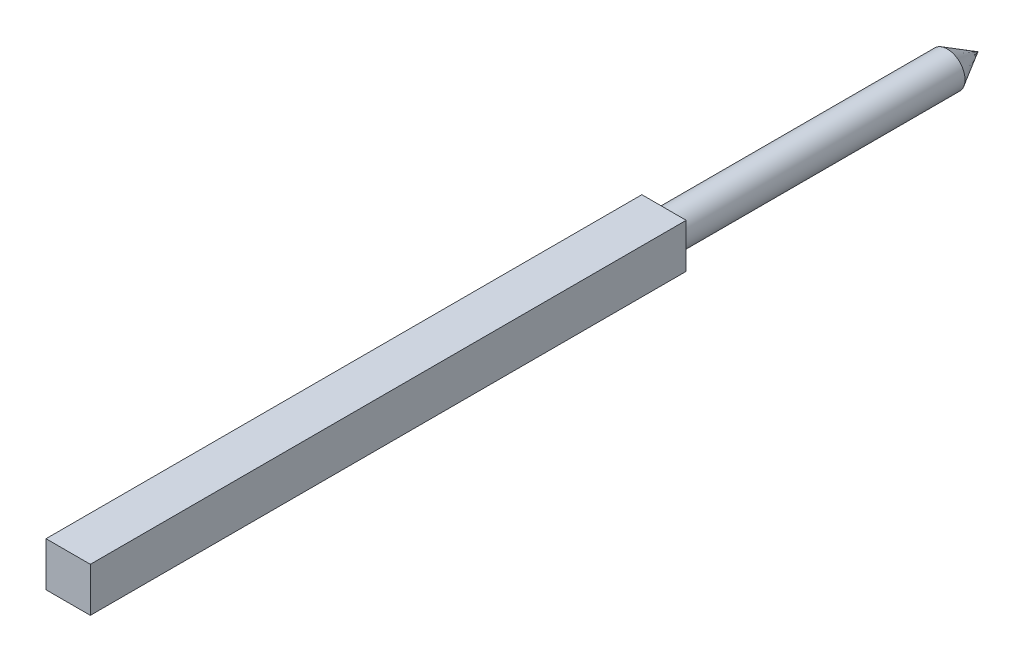
SolidWorks part; units mm, degrees
ref_plane "Front Plane" through (0, 0, 0) normal (0, 0, 1) x (1, 0, 0)
ref_plane "Top Plane" through (0, 0, 0) normal (0, 1, 0) x (1, 0, 0)
ref_plane "Right Plane" through (0, 0, 0) normal (1, 0, 0) x (0, 0, -1)
sketch "Sketch1" plane through (0, 0, 0) normal (0, 0, 1) x (1, 0, 0)
  line L1 (-3.1306, -3.1242) -> (3.1305, -3.1242)
  line L2 (-3.1306, -3.1242) -> (-3.1306, 3.1242)
  line L3 (-3.1306, 3.1242) -> (3.1305, 3.1242)
  line L4 (3.1305, -3.1242) -> (3.1305, 3.1242)
  line L5 (-3.1306, -3.1242) -> (3.1305, 3.1242) construction
  line L6 (-3.1306, 3.1242) -> (3.1305, -3.1242) construction
  circle A0 centre (0, 0) radius 2.5
  point P0 (0, 0)
  dimension "D3" = 5
  dimension "D1" = 6.2484
  dimension "D2" = 6.2611
extrude "Boss-Extrude1" add sketch "Sketch1" along normal blind 84.1375 contours L2 L3 L4 L1
extrude "Boss-Extrude2" add sketch "Sketch1<4>" against normal blind 40.005 contours A0
sketch "Sketch1<4>" plane through (0, 0, 0) normal (0, 0, 1) x (1, 0, 0) same geometry as "Sketch1"
sketch "Sketch6" plane through (0, 0, -40.005) normal (0, 0, -1) x (-1, 0, 0)
  circle A0 centre (0, 0) radius 2.5 construction
  circle A1 centre (0, 0) radius 2.5
extrude "Boss-Extrude3" add sketch "Sketch6" along normal blind 40 draft 30
